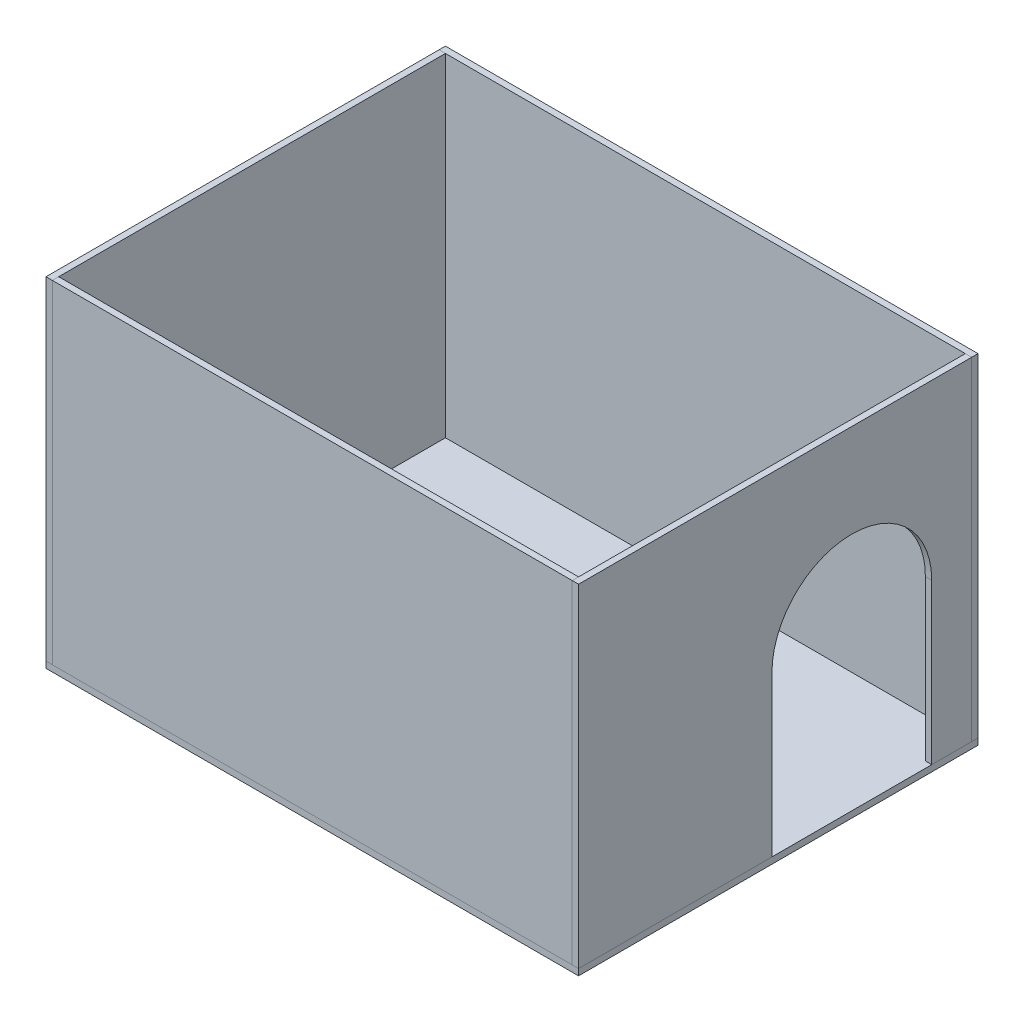
SolidWorks part; units mm, degrees
ref_plane "Front Plane" through (0, 0, 0) normal (0, 0, 1) x (1, 0, 0)
ref_plane "Top Plane" through (0, 0, 0) normal (0, 1, 0) x (1, 0, 0)
ref_plane "Right Plane" through (0, 0, 0) normal (1, 0, 0) x (0, 0, -1)
sketch "base" plane through (0, 0, 0) normal (0, 1, 0) x (1, 0, 0)
  line L1 (0, 0) -> (400, 0)
  line L2 (0, 0) -> (0, 300)
  line L3 (0, 300) -> (400, 300)
  line L4 (400, 0) -> (400, 300)
  dimension "D1" = 300
  dimension "D2" = 400
extrude "base-extrude" add sketch "base" along normal blind 4.76
sketch "Sketch2" plane through (0, 0, 0) normal (0, 1, 0) x (1, 0, 0)
  line L0 (400, 0) -> (400, 300) construction
  line L1 (0, 300) -> (400, 300)
  line L2 (0, 300) -> (0, 295.24)
  line L3 (0, 295.24) -> (400, 295.24)
  line L4 (400, 300) -> (400, 295.24)
  line L5 (0, 0) -> (400, 0) construction
  line L6 (4.76, 0) -> (0, 0)
  line L7 (4.76, 0) -> (4.76, 295.24)
  line L8 (4.76, 295.24) -> (0, 295.24)
  line L9 (0, 0) -> (0, 295.24)
  line L11 (4.76, 4.76) -> (395.24, 4.76)
  line L12 (4.76, 4.76) -> (4.76, 0)
  line L13 (4.76, 0) -> (395.24, 0)
  line L14 (395.24, 4.76) -> (395.24, 0)
  line L15 (395.24, 0) -> (400, 0)
  line L16 (395.24, 0) -> (395.24, 295.24)
  line L17 (395.24, 295.24) -> (400, 295.24)
  line L18 (400, 0) -> (400, 295.24)
  dimension "D1" = 4.76
  dimension "D2" = 4.76
  dimension "D3" = 4.76
  dimension "D4" = 4.76
extrude "Boss-Extrude2" add sketch "Sketch2" along normal blind 250 from surface separate body contours L9 L6 L7 L3 region at (2.38, 0, -147.62) starting at face at (200, 4.76, -150)
extrude "Boss-Extrude3" add sketch "Sketch2<3>" along normal blind 250 from surface separate body contours L4 L1 L2 L3 region at (200, 0, -297.62) starting at face at (200, 4.76, -150)
sketch "Sketch2<3>" plane through (0, 0, 0) normal (0, 1, 0) x (1, 0, 0) same geometry as "Sketch2"
extrude "Boss-Extrude4" add sketch "Sketch2<4>" along normal blind 250 from surface separate body contours L15 L18 L3 L16 L14 region at (397.62, 0, -147.62) starting at face at (200, 4.76, -150)
sketch "Sketch2<4>" plane through (0, 0, 0) normal (0, 1, 0) x (1, 0, 0) same geometry as "Sketch2"
extrude "Boss-Extrude5" add sketch "Sketch2<5>" along normal blind 250 from surface separate body contours L14 L11 L7 L13 region at (200, 0, -2.38) starting at face at (200, 4.76, -150)
sketch "Sketch2<5>" plane through (0, 0, 0) normal (0, 1, 0) x (1, 0, 0) same geometry as "Sketch2"
sketch "Sketch3" plane through (400, 0, 0) normal (1, 0, 0) x (0, 0, -1)
  line L0 (145.24, 4.76) -> (145.24, 124.76)
  line L1 (0, 4.76) -> (295.24, 4.76) construction
  line L2 (295.24, 254.76) -> (295.24, 4.76) construction
  line L3 (265.24, 124.76) -> (265.24, 4.76)
  line L4 (265.24, 4.76) -> (145.24, 4.76)
  arc A0 (145.24, 124.76) -> (265.24, 124.76) centre (205.24, 124.76) cw
  dimension "D1" = 120
  dimension "D2" = 120
  dimension "D3" = 30
extrude "Cut-Extrude1" cut sketch "Sketch3" against normal blind 5
